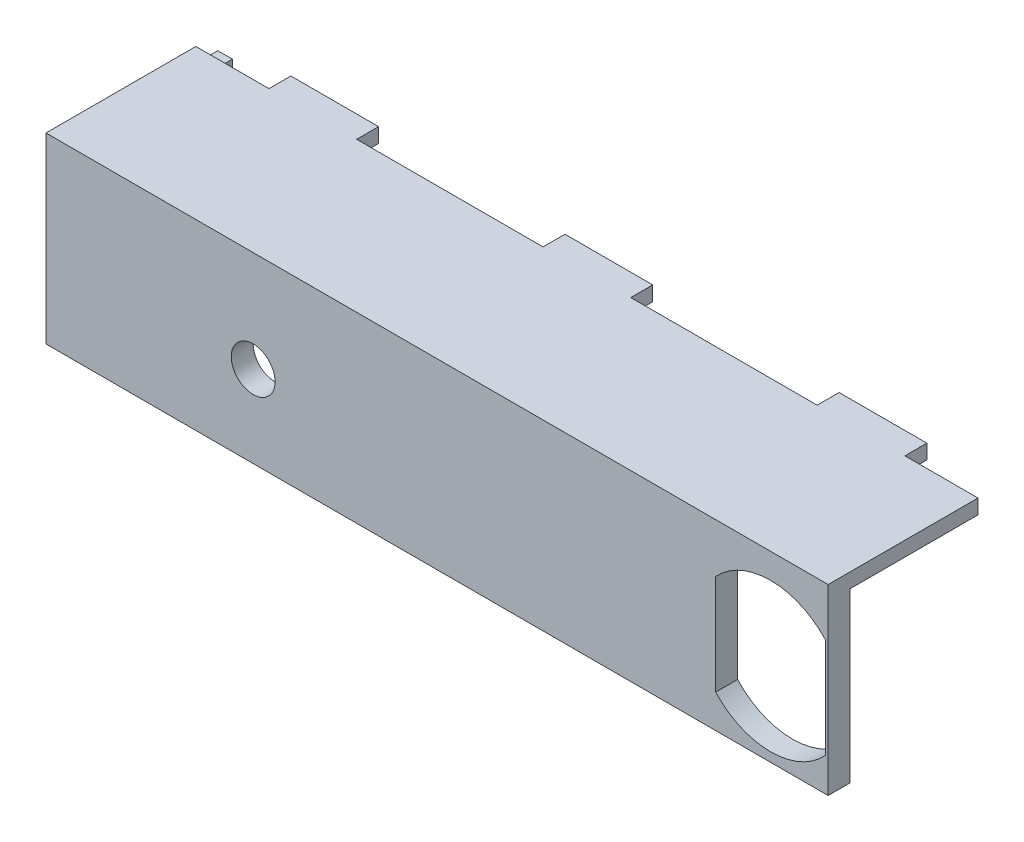
SolidWorks part; units mm, degrees
note: The reader was unsure of these and kept them because the rebuilt part matched: shared geometry of "Esboço1<11>", "Esboço1<12>", "Esboço1<13>", "Esboço1<14>", "Esboço1<15>".
ref_plane "Plano frontal" through (0, 0, 0) normal (0, 0, 1) x (1, 0, 0)
ref_plane "Plano superior" through (0, 0, 0) normal (0, 1, 0) x (1, 0, 0)
ref_plane "Plano direito" through (0, 0, 0) normal (1, 0, 0) x (0, 0, -1)
sketch "Esboço1" plane through (0, 0, 0) normal (0, 0, 1) x (1, 0, 0)
  line L0 (65.9416, 26.5399) -> (65.9416, 12.8399)
  line L1 (-40.6777, 33.2717) -> (66.3223, 33.2717)
  line L2 (-40.6777, 33.2717) -> (-40.6777, 8.2717)
  line L3 (-40.6777, 8.2717) -> (66.3223, 8.2717)
  line L4 (66.3223, 33.2717) -> (66.3223, 8.2717)
  line L5 (50.9416, 26.5399) -> (50.9416, 12.8399)
  line L6 (66.3223, 31.2717) -> (-40.6777, 31.2717)
  line L7 (-38.6777, 31.2717) -> (-38.6777, 8.2717)
  line L8 (56.3223, 33.2717) -> (44.3223, 33.2717)
  line L9 (56.3223, 33.2717) -> (56.3223, 31.2717)
  line L10 (56.3223, 31.2717) -> (44.3223, 31.2717)
  line L11 (44.3223, 33.2717) -> (44.3223, 31.2717)
  line L12 (-30.6777, 33.2717) -> (-18.6777, 33.2717)
  line L13 (-30.6777, 33.2717) -> (-30.6777, 31.2717)
  line L14 (-30.6777, 31.2717) -> (-18.6777, 31.2717)
  line L15 (-18.6777, 33.2717) -> (-18.6777, 31.2717)
  line L16 (-38.6777, 16.2717) -> (-40.6777, 16.2717)
  line L17 (-38.6777, 31.2717) -> (-40.6777, 31.2717)
  line L18 (-38.6777, 31.2717) -> (-38.6777, 25.2717)
  line L19 (-38.6777, 25.2717) -> (-40.6777, 25.2717)
  line L20 (-40.6777, 31.2717) -> (-40.6777, 25.2717)
  line L21 (-38.6777, 10.2717) -> (-40.6777, 10.2717)
  line L23 (18.8223, 33.2717) -> (6.8223, 33.2717)
  line L24 (18.8223, 33.2717) -> (18.8223, 31.2717)
  line L25 (18.8223, 31.2717) -> (6.8223, 31.2717)
  line L26 (6.8223, 33.2717) -> (6.8223, 31.2717)
  circle A0 centre (14.3223, 15.1717) radius 1.5
  circle A1 centre (31.8223, 15.1717) radius 1.5
  circle A2 centre (58.4416, 19.6899) radius 1
  circle A3 centre (14.3223, 15.1717) radius 3.5
  circle A4 centre (31.8223, 15.1717) radius 3.5
  arc A5 (65.9416, 26.5399) -> (50.9416, 26.5399) centre (58.4416, 19.6299) ccw
  circle A6 centre (49.3223, 15.1717) radius 1.5 [skipped]
  circle A7 centre (49.3223, 15.1717) radius 3.5 [skipped]
  arc A8 (65.9416, 12.8399) -> (50.9416, 12.8399) centre (58.4416, 19.6462) cw
  circle A9 centre (-12.3361, 19.4528) radius 3
  point P4 (14.3223, 8.2717)
  point P5 (14.3223, 8.2717)
  point P17 (65.9416, 19.6899)
  point P24 (50.9416, 19.6899)
  point P51 (12.8223, 33.2717)
  dimension "D4" = 3
  dimension "D7" = 7
  dimension "D11" = 2
  dimension "D19" = 6
  dimension "D1" = 107
  dimension "D2" = 25
  dimension "D3" = 55
  dimension "D5" = 6.9
  dimension "D6" = 3
  dimension "D9" = 17.5
  dimension "D10" = 17.5
  dimension "D12" = 27
  dimension "D13" = 7.5
  dimension "D14" = 7.5
  dimension "D15" = 13.7
  dimension "D16" = 0
  dimension "D17" = 13.7
  dimension "D18" = 0
  dimension "D20" = 27
  dimension "D21" = 2
  dimension "D22" = 10
  dimension "D23" = 12
  dimension "D24" = 12
  dimension "D25" = 10
  dimension "D26" = 2
  dimension "D27" = 6
  dimension "D28" = 2
  dimension "D29" = 6
  dimension "D30" = 6
  dimension "D31" = 6
  dimension "D8" = 3
extrude "Ressalto-extrusão1" add sketch "Esboço1" against normal blind 3 contours L6 L7 L3 L4 A9 A3 A4 L0 A8 L5 A5 | A4 A1 | A1 | A0 | A3 A0 | L1 L9 L6 L4 | L1 L11 L6 L9 | L1 L24 L6 L11 | L1 L26 L6 L24 | L26 L1 L15 L6 | L15 L1 L13 L6 | L13 L1 L2 L6 | L19 L7 L6 L2 | L7 L19 L2 L16 | L21 L7 L16 L2 | L7 L21 L2 L3
extrude "Ressalto-extrusão2" add sketch "Esboço1<11>" against normal blind 20.5 contours L1 L11 L6 L9 | L1 L9 L6 L4 | L1 L24 L6 L11 | L1 L26 L6 L24 | L26 L1 L15 L6 | L15 L1 L13 L6 | L13 L1 L2 L6 | L19 L7 L6 L2 | L7 L19 L2 L16 | L21 L7 L16 L2 | L7 L21 L2 L3
sketch "Esboço1<11>" plane through (0, 0, 0) normal (0, 0, 1) x (1, 0, 0) same geometry as "Esboço1"
extrude "Ressalto-extrusão3" add sketch "Esboço1<12>" against normal blind 23.5 contours L1 L11 L6 L9 | L1 L26 L6 L24 | L15 L1 L13 L6 | L19 L7 L6 L2 | L21 L7 L16 L2
sketch "Esboço1<12>" plane through (0, 0, 0) normal (0, 0, 1) x (1, 0, 0) same geometry as "Esboço1"
extrude "Ressalto-extrusão4" add sketch "Esboço1<13>" against normal blind 5 contours A4 | A3
sketch "Esboço1<13>" plane through (0, 0, 0) normal (0, 0, 1) x (1, 0, 0) same geometry as "Esboço1"
extrude "Corte-extrusão1" cut sketch "Esboço1<14>" against normal blind 5 contours A1 | A0
sketch "Esboço1<14>" plane through (0, 0, 0) normal (0, 0, 1) x (1, 0, 0) same geometry as "Esboço1"
extrude "Ressalto-extrusão5" add sketch "Esboço1<15>" against normal blind 3 contours A1 | A0
sketch "Esboço1<15>" plane through (0, 0, 0) normal (0, 0, 1) x (1, 0, 0) same geometry as "Esboço1"
